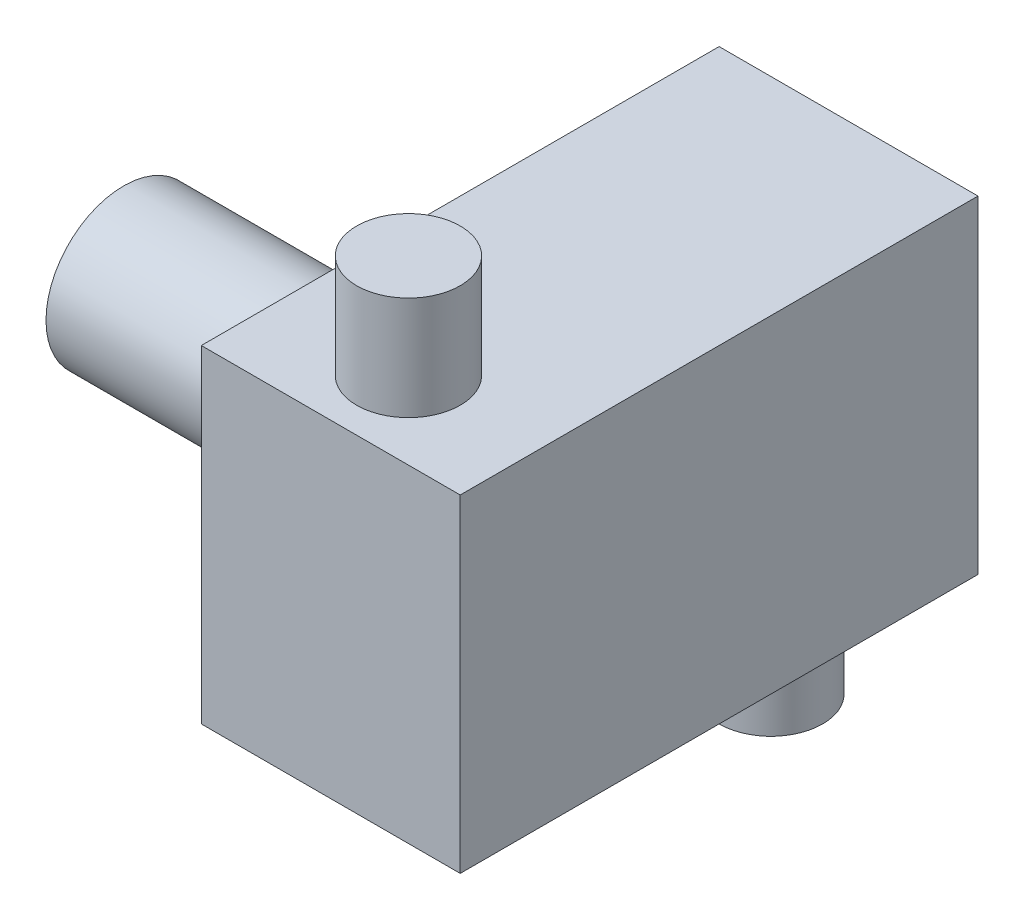
SolidWorks part; units mm, degrees
ref_plane "Front Plane" through (0, 0, 0) normal (0, 0, 1) x (1, 0, 0)
ref_plane "Top Plane" through (0, 0, 0) normal (0, 1, 0) x (1, 0, 0)
ref_plane "Right Plane" through (0, 0, 0) normal (1, 0, 0) x (0, 0, -1)
sketch "Sketch1" plane through (0, 0, 0) normal (0, 1, 0) x (1, 0, 0)
  line L1 (0, 0) -> (5, 0)
  line L2 (0, 0) -> (0, -10)
  line L3 (0, -10) -> (5, -10)
  line L4 (5, 0) -> (5, -10)
  dimension "D1" = 5
  dimension "D2" = 10
extrude "Boss-Extrude1" add sketch "Sketch1" along normal blind 6.33
sketch "Sketch2" plane through (0, 6.33, 0) normal (0, 1, 0) x (1, 0, 0)
  line L0 (5, -8.5) -> (0, -8.5) construction
  line L1 (5, -10) -> (5, 0) construction
  line L2 (0, 0) -> (0, -10) construction
  line L3 (2.5, -9.5) -> (2.5, -10) construction
  line L4 (0, -10) -> (5, -10) construction
  circle A0 centre (2.5, -8.5) radius 1
  dimension "D1" = 2
  dimension "D2" = 0.5
extrude "Boss-Extrude2" add sketch "Sketch2" along normal blind 2
sketch "Sketch3" plane through (0, 0, 0) normal (-1, 0, 0) x (0, 0, 1)
  line L1 (5, 1.75) -> (5, 0) construction
  line L4 (0, 0) -> (10, 0) construction
  circle A0 centre (5, 1.75) radius 1.5
  dimension "D1" = 3
  dimension "D2" = 1.75
extrude "Boss-Extrude3" add sketch "Sketch3" along normal blind 6.5
sketch "Sketch4" plane through (0, 0, 0) normal (0, -1, 0) x (1, 0, 0)
  line L0 (2.5, 0.5) -> (2.5, 0) construction
  line L1 (5, 0) -> (0, 0) construction
  line L2 (0, 1.5) -> (5, 1.5) construction
  line L3 (0, 0) -> (0, 10) construction
  line L4 (5, 10) -> (5, 0) construction
  circle A0 centre (2.5, 1.5) radius 1
  dimension "D1" = 2
  dimension "D2" = 0.5
extrude "Boss-Extrude4" add sketch "Sketch4" along normal blind 2.5
fillet "Fillet1" radius 0.75 1 edges at (0, 1.75, 3.5)
